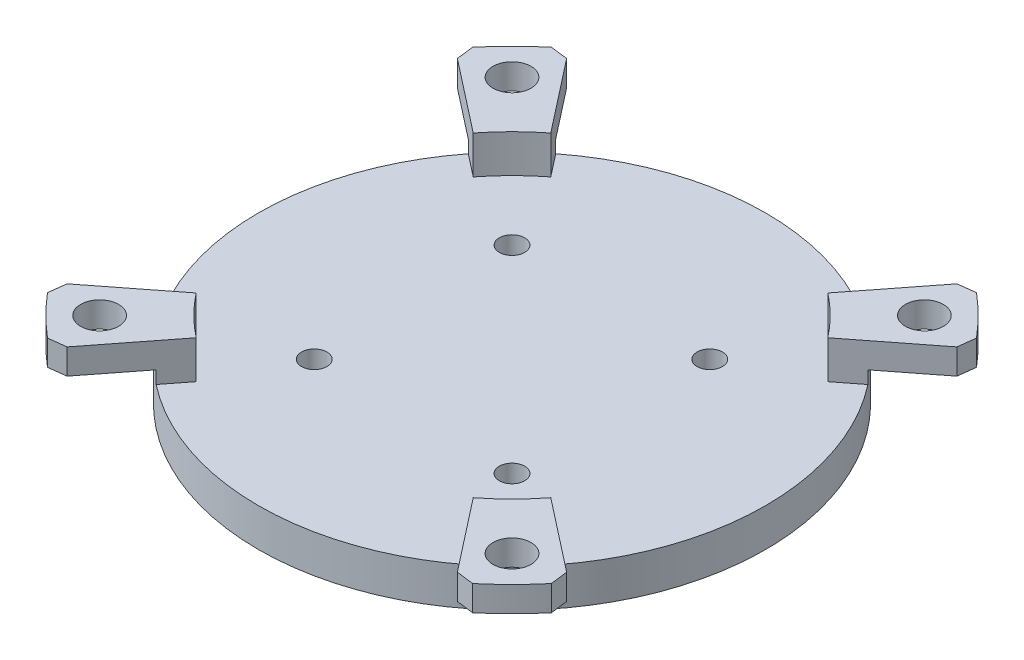
SolidWorks part; units mm, degrees
ref_plane "Front Plane" through (0, 0, 0) normal (0, 0, 1) x (1, 0, 0)
ref_plane "Top Plane" through (0, 0, 0) normal (0, 1, 0) x (1, 0, 0)
ref_plane "Right Plane" through (0, 0, 0) normal (1, 0, 0) x (0, 0, -1)
sketch "Sketch1" plane through (0, 0, 0) normal (0, 1, 0) x (1, 0, 0)
  circle A0 centre (0, 0) radius 20
  circle A1 centre (-7.8, 7.8) radius 1
  circle A2 centre (7.8, 7.8) radius 1
  circle A3 centre (7.8, -7.8) radius 1
  circle A4 centre (-7.8, -7.8) radius 1
  dimension "D1" = 40
  dimension "D2" = 2
  dimension "D3" = 7.8
  dimension "D4" = 7.8
  dimension "D5" = 2
  dimension "D6" = 2
extrude "Boss-Extrude1" add sketch "Sketch1" along normal blind 3
sketch "Sketch2" plane through (0, 3, 0) normal (0, 1, 0) x (1, 0, 0)
  line L0 (0, 0) -> (-14.1421, 14.1421) construction
  line L1 (-10.9263, 13.9851) -> (-12.3132, 15.7602)
  line L2 (-13.9851, 10.9263) -> (-15.7602, 12.3132)
  line L3 (-1.65, 0) -> (1.65, 0) construction
  line L4 (10.9263, 13.9851) -> (12.3132, 15.7602)
  line L5 (13.9851, 10.9263) -> (15.7602, 12.3132)
  line L6 (13.9851, -10.9263) -> (15.7602, -12.3132)
  line L7 (10.9263, -13.9851) -> (12.3132, -15.7602)
  line L8 (-10.9263, -13.9851) -> (-12.3132, -15.7602)
  line L9 (-13.9851, -10.9263) -> (-15.7602, -12.3132)
  arc A0 (-12.3132, 15.7602) -> (-15.7602, 12.3132) centre (0, 0) ccw
  arc A1 (-10.9263, 13.9851) -> (-13.9851, 10.9263) centre (0, 0) ccw
  arc A2 (15.7602, 12.3132) -> (12.3132, 15.7602) centre (0, 0) ccw
  arc A3 (13.9851, 10.9263) -> (10.9263, 13.9851) centre (0, 0) ccw
  arc A4 (12.3132, -15.7602) -> (15.7602, -12.3132) centre (0, 0) ccw
  arc A5 (10.9263, -13.9851) -> (13.9851, -10.9263) centre (0, 0) ccw
  arc A6 (-15.7602, -12.3132) -> (-12.3132, -15.7602) centre (0, 0) ccw
  arc A7 (-13.9851, -10.9263) -> (-10.9263, -13.9851) centre (0, 0) ccw
  point P24 (0, 0)
  dimension "D1" = 7
  dimension "D2" = 7
  dimension "D3" = 45
  dimension "D4" = 4
extrude "Boss-Extrude2" add sketch "Sketch2" along normal blind 3
sketch "Sketch3" plane through (0, 6, 0) normal (0, 1, 0) x (1, 0, 0)
  line L0 (12.3132, 15.7602) -> (16.0072, 20.4883)
  line L1 (-12.3132, 15.7602) -> (-16.0072, 20.4883)
  line L2 (15.7602, 12.3132) -> (20.4883, 16.0072)
  line L3 (-15.7602, 12.3132) -> (-20.4883, 16.0072)
  line L4 (15.7602, -12.3132) -> (20.4883, -16.0072)
  line L5 (12.3132, -15.7602) -> (16.0072, -20.4883)
  line L6 (-12.3132, -15.7602) -> (-16.0072, -20.4883)
  line L7 (-15.7602, -12.3132) -> (-20.4883, -16.0072)
  arc A0 (-12.3132, 15.7602) -> (-15.7602, 12.3132) centre (0, 0) ccw
  arc A1 (-16.0072, 20.4883) -> (-20.4883, 16.0072) centre (0, 0) ccw
  arc A2 (15.7602, 12.3132) -> (12.3132, 15.7602) centre (0, 0) ccw
  arc A3 (20.4883, 16.0072) -> (16.0072, 20.4883) centre (0, 0) ccw
  arc A4 (12.3132, -15.7602) -> (15.7602, -12.3132) centre (0, 0) ccw
  arc A5 (16.0072, -20.4883) -> (20.4883, -16.0072) centre (0, 0) ccw
  arc A6 (-15.7602, -12.3132) -> (-12.3132, -15.7602) centre (0, 0) ccw
  arc A7 (-20.4883, -16.0072) -> (-16.0072, -20.4883) centre (0, 0) ccw
  point P1 (-42.6384, 3.0569)
  point P3 (-43.8506, 8.9599)
  point P23 (0, 0)
  dimension "D2" = 52
  dimension "D3" = 4
extrude "Boss-Extrude3" add sketch "Sketch3" against normal blind 2
sketch "Sketch4" plane through (0, 4, 0) normal (0, -1, 0) x (1, 0, 0)
  line L0 (-18.3848, -18.3848) -> (-14.1421, -14.1421) construction
  arc A0 (-20.4883, -16.0072) -> (-16.0072, -20.4883) centre (0, 0) ccw construction
  arc A1 (-15.7602, -12.3132) -> (-12.3132, -15.7602) centre (0, 0) ccw construction
  circle A2 centre (-16.2635, -16.2635) radius 1.5
  circle A3 centre (-16.2635, 16.2635) radius 1.5
  circle A4 centre (16.2635, 16.2635) radius 1.5
  circle A5 centre (16.2635, -16.2635) radius 1.5
  point P19 (0, 0)
  dimension "D1" = 3
  dimension "D2" = 4
extrude "Cut-Extrude1" cut sketch "Sketch4" against normal blind 2
chamfer "Chamfer2" distance 1 angle 45 8 edges at (-16.0072, 5, 20.4883) (-20.4883, 5, 16.0072) (16.0072, 5, 20.4883) (20.4883, 5, 16.0072) (20.4883, 5, -16.0072) (16.0072, 5, -20.4883) (-20.4883, 5, -16.0072) (-16.0072, 5, -20.4883)
